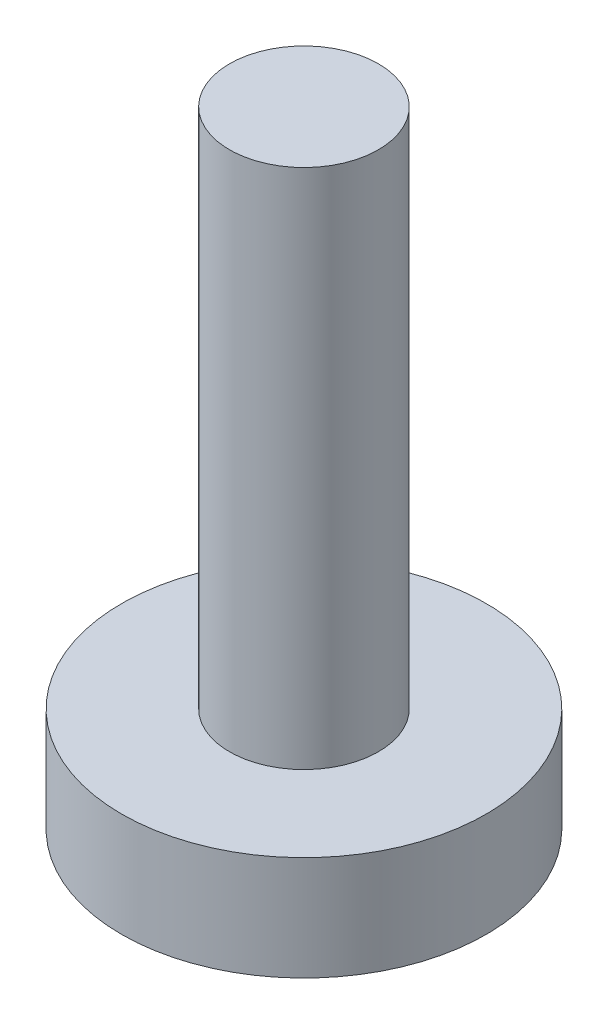
SolidWorks part; units mm, degrees
ref_plane "Front Plane" through (0, 0, 0) normal (0, 0, 1) x (1, 0, 0)
ref_plane "Top Plane" through (0, 0, 0) normal (0, 1, 0) x (1, 0, 0)
ref_plane "Right Plane" through (0, 0, 0) normal (1, 0, 0) x (0, 0, -1)
sketch "Sketch2" plane through (0, 0, 0) normal (0, 1, 0) x (1, 0, 0)
  circle A0 centre (0, 0) radius 6.12
  circle A1 centre (0, 0) radius 2.5
  dimension "D1" = 12.24
  dimension "D2" = 5
extrude "Boss-Extrude1" add sketch "Sketch2" along normal blind 3.5
extrude "Boss-Extrude2" add sketch "Sketch2<2>" along normal blind 21 contours A1 region at (0, 0, 0)
sketch "Sketch2<2>" plane through (0, 0, 0) normal (0, 1, 0) x (1, 0, 0) same geometry as "Sketch2"
